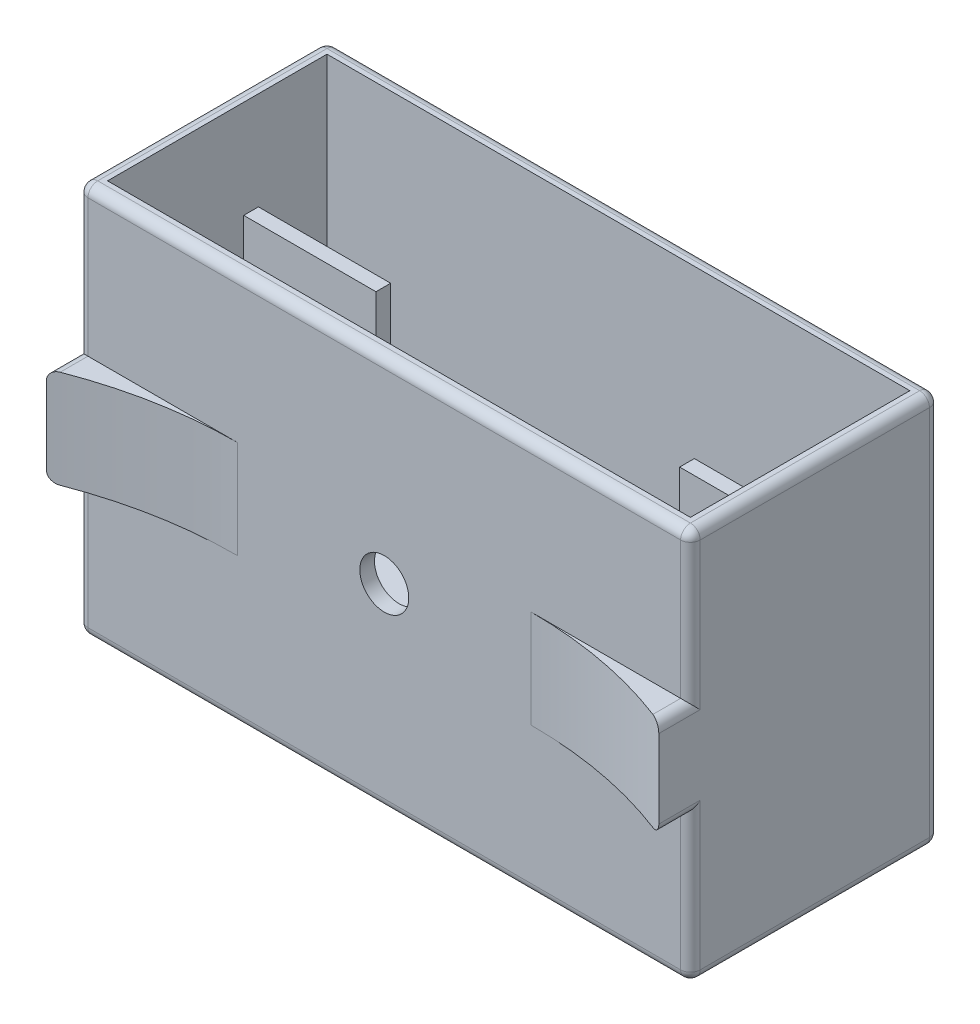
SolidWorks part; units mm, degrees
ref_plane "Front Plane" through (0, 0, 0) normal (0, 0, 1) x (1, 0, 0)
ref_plane "Top Plane" through (0, 0, 0) normal (0, 1, 0) x (1, 0, 0)
ref_plane "Right Plane" through (0, 0, 0) normal (1, 0, 0) x (0, 0, -1)
sketch "Sketch13" plane through (0, 0, 0) normal (0, 1, 0) x (1, 0, 0)
  line L1 (15, -5) -> (-15, -5)
  line L2 (15, -5) -> (15, 5)
  line L3 (15, 5) -> (-15, 5)
  line L4 (-15, -5) -> (-15, 5)
  line L5 (15, -5) -> (-15, 5) construction
  line L6 (15, 5) -> (-15, -5) construction
  line L12 (0.4631, -5) -> (-15, -5)
  line L17 (-26.2048, -5) -> (-15, -5)
  line L44 (-31.25, 30.4) -> (31.25, 30.4)
  line L45 (-31.25, 30.4) -> (-31.25, 5)
  line L46 (-31.25, 5) -> (31.25, 5)
  line L47 (31.25, 30.4) -> (31.25, 5)
  line L59 (0, 0) -> (0, 17.537) construction
  line L60 (-31.25, 1.7707) -> (31.25, 1.7707)
  line L61 (-31.25, 1.7707) -> (-31.25, 30.4)
  line L62 (-31.25, 30.4) -> (31.25, 30.4)
  line L63 (31.25, 1.7707) -> (31.25, 30.4)
  circle A3 centre (-15, -37.5) radius 42.5
  circle A4 centre (-15, -37.5) radius 32.5
  circle A5 centre (15, -37.5) radius 42.5
  circle A6 centre (15, -37.5) radius 32.5
  point P0 (0, 0)
  point P46 (0, 30.4)
  dimension "D4" = 85
  dimension "D1" = 30
  dimension "D2" = 10
  dimension "D18" = 62.5
  dimension "D19" = 25.4
extrude "Boss-Extrude1" add sketch "Sketch13" along normal mid plane 10 contours A3 L46 L61 | L47 L44 L45 L46 L3 | A5 L63 L46 region at (0, 0, -17.7) region at (27.219, 0, -4.0379) region at (-27.219, 0, -4.0379)
extrude "Boss-Extrude2" add sketch "Sketch13<12>" along normal mid plane 40 contours L47 L44 L45 L46 L3 region at (0, 0, -17.7)
sketch "Sketch13<12>" plane through (0, 0, 0) normal (0, 1, 0) x (1, 0, 0) same geometry as "Sketch13"
shell "Shell1" thickness 1.5 removed face at (0, 20, -17.7)
sketch "Sketch14" plane through (0, 0, -5) normal (0, 0, 1) x (1, 0, 0)
  circle A0 centre (0, 0) radius 2.5
  dimension "D1" = 5
extrude "Cut-Extrude1" cut sketch "Sketch14" against normal up to surface (1.5 mm away) from surface up to face at (0, 0.25, -6.5) starting at face at (0, 0, -5)
sketch "Sketch15" plane through (0, 0, 0) normal (0, 1, 0) x (1, 0, 0)
  line L0 (-29.75, 28.9) -> (-29.75, 6.5) construction
  line L1 (-29.75, 20.4) -> (-16.25, 20.4)
  line L2 (-29.75, 20.4) -> (-29.75, 21.9)
  line L3 (-29.75, 21.9) -> (-16.25, 21.9)
  line L4 (-16.25, 20.4) -> (-16.25, 21.9)
  line L5 (29.75, 28.9) -> (29.75, 6.5) construction
  line L6 (29.75, 21.9) -> (14.75, 21.9)
  line L7 (29.75, 21.9) -> (29.75, 20.4)
  line L8 (29.75, 20.4) -> (14.75, 20.4)
  line L9 (14.75, 21.9) -> (14.75, 20.4)
  line L11 (-29.75, 28.9) -> (29.75, 28.9) construction
  line L12 (-29.75, 28.9) -> (29.75, 28.9) construction
  line L13 (-31.25, 30.4) -> (-31.25, 5) construction
  dimension "D1" = 7
  dimension "D2" = 7
  dimension "D3" = 15
  dimension "D4" = 15
  dimension "D5" = 1.5
  dimension "D6" = 1.5
extrude "Boss-Extrude3" add sketch "Sketch15" along normal mid plane 20
fillet "Fillet21" radius 1 18 edges at (0, -20, -5) (-31.25, -20, -17.7) (0, -20, -30.4) (-31.25, 0, -30.4) (0, 20, -30.4) (31.25, 20, -17.7) (31.25, 0, -30.4) (31.25, -20, -17.7) (31.25, -12.5, -5) (31.25, -5, -3.3853) (31.25, 5, -3.3853) (31.25, 12.5, -5) (0, 20, -5) (-31.25, 20, -17.7) (-31.25, -12.5, -5) (-31.25, -5, -3.3853) (-31.25, 5, -3.3853) (-31.25, 12.5, -5)
sketch "Sketch16" plane through (0, 0, 0) normal (0, 1, 0) x (1, 0, 0)
  line L1 (30.25, 5) -> (-30.25, 5) construction
  circle A0 centre (0, 10) radius 2.5
  point P2 (-16.038, 11.3433)
  point P3 (0, 10.5777)
  point P4 (0, 0)
  dimension "D1" = 5
  dimension "D2" = 5
extrude "Cut-Extrude2" cut sketch "Sketch16" against normal up to surface (20 mm away) from surface up to face at (0, -20, -17.7) starting at face at (0, -18.5, -17.7)
equation "\"0..5cm\"=0.9"
equation "\"0.1.5cm\"=0.75"
equation "\"1..25cm\"=1.75"
